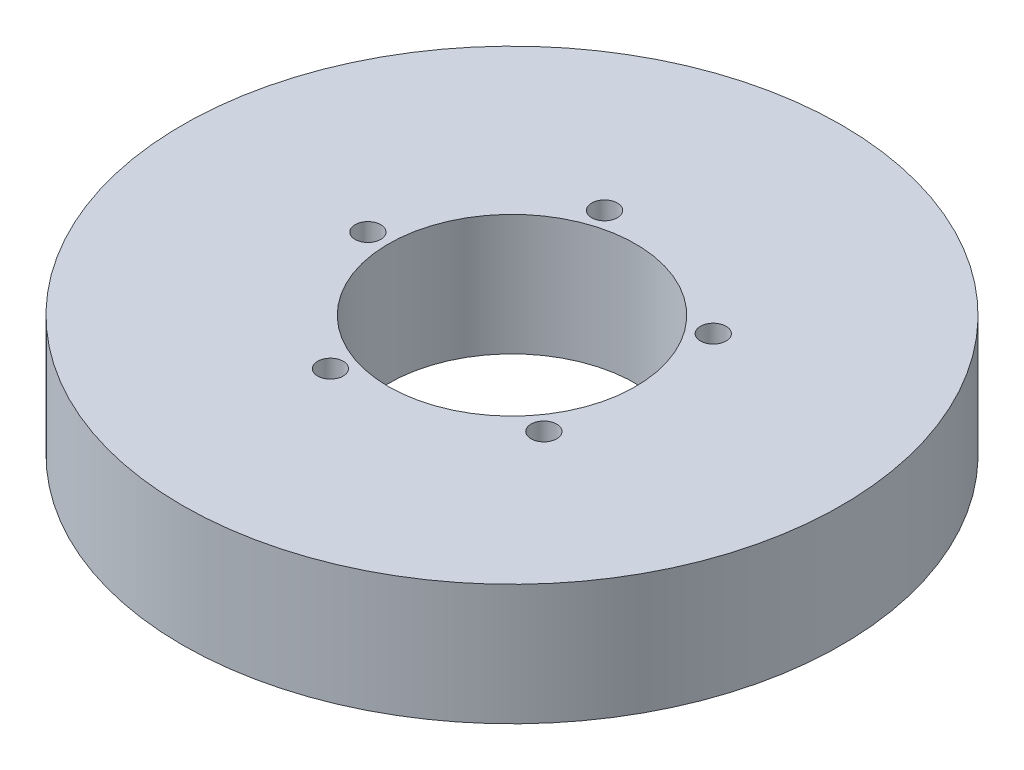
SolidWorks part; units mm, degrees
ref_plane "Front Plane" through (0, 0, 0) normal (0, 0, 1) x (1, 0, 0)
ref_plane "Top Plane" through (0, 0, 0) normal (0, 1, 0) x (1, 0, 0)
ref_plane "Right Plane" through (0, 0, 0) normal (1, 0, 0) x (0, 0, -1)
sketch "Sketch1" plane through (0, 0, 0) normal (0, 1, 0) x (1, 0, 0)
  circle A0 centre (0, 0) radius 60
  dimension "FLANGE_OD" = 120
extrude "Boss-Extrude1" add sketch "Sketch1" along normal blind 22
sketch "Sketch2" plane through (0, 0, 0) normal (0, 1, 0) x (1, 0, 0)
  circle A0 centre (0, 0) radius 22.5
  dimension "BORE_D" = 45
extrude "Cut-Extrude1" cut sketch "Sketch2" along normal through all
sketch "Sketch3" plane through (0, 22, 0) normal (0, 1, 0) x (1, 0, 0)
  circle A0 centre (0, 0) radius 26.2343 construction
  circle A1 centre (-26.2343, 0) radius 2.3361
  dimension "BOLT_D" = 4.6722
  dimension "BOLT_PCD" = 52.4687
extrude "Cut-Extrude2" cut sketch "Sketch3" against normal blind 20.0416
pattern_circular "CirPattern1" count 5 over 360 about axis through (0, 0, 0) along (0, 1, 0) of "Cut-Extrude2"
